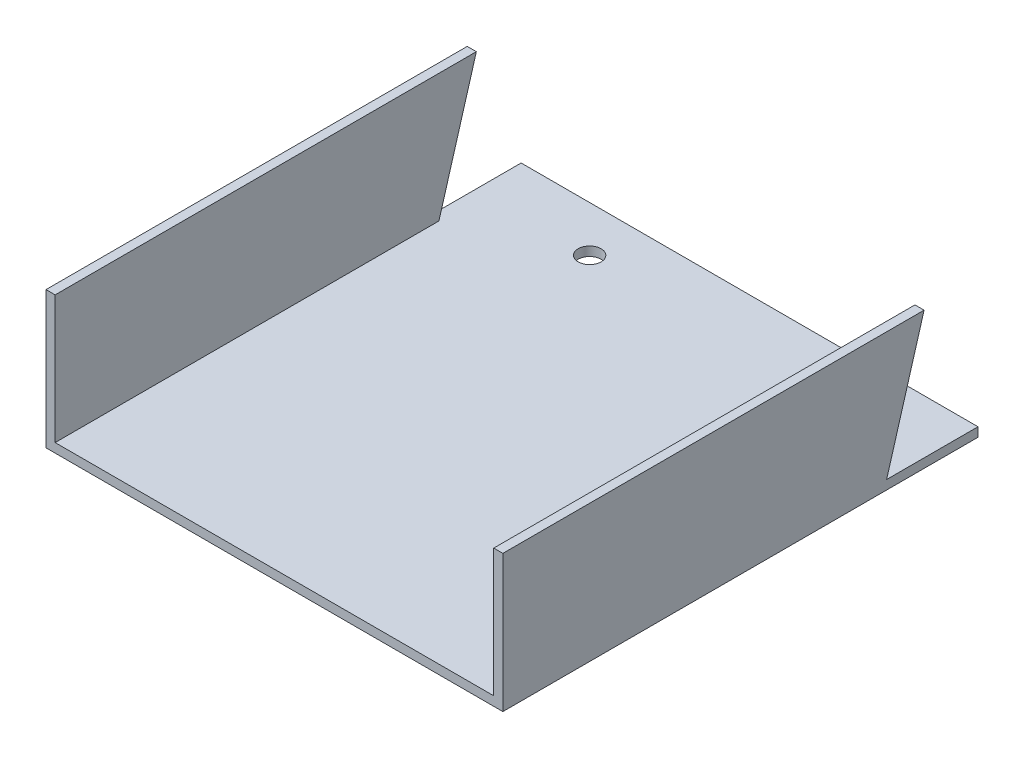
SolidWorks part; units mm, degrees
ref_plane "Front Plane" through (0, 0, 0) normal (0, 0, 1) x (1, 0, 0)
ref_plane "Top Plane" through (0, 0, 0) normal (0, 1, 0) x (1, 0, 0)
ref_plane "Right Plane" through (0, 0, 0) normal (1, 0, 0) x (0, 0, -1)
sketch "Sketch1" plane through (0, 0, 0) normal (0, 0, 1) x (1, 0, 0)
  line L0 (0, 0) -> (127, 0)
  line L1 (127, 0) -> (127, 38.1)
  line L2 (127, 38.1) -> (0, 38.1)
  line L3 (0, 38.1) -> (0, 0)
  dimension "D1" = 127
  dimension "D2" = 38.1
extrude "Boss-Extrude1" add sketch "Sketch1" along normal blind 132.08
sketch "Sketch2" plane through (0, 38.1, 0) normal (0, 1, 0) x (1, 0, 0)
  line L4 (0, -25.4) -> (2.54, -25.4)
  line L5 (2.54, -25.4) -> (2.54, -132.08)
  line L6 (63.5, 0) -> (63.5, -132.08) construction
  line L7 (124.46, -25.4) -> (124.46, -132.08)
  line L8 (127, 0) -> (0, 0)
  line L9 (0, 0) -> (0, -132.08)
  line L10 (0, -132.08) -> (127, -132.08)
  line L11 (127, -132.08) -> (127, 0)
  line L12 (127, 0) -> (0, 0)
  line L13 (0, 0) -> (0, -25.4)
  line L14 (2.54, -132.08) -> (124.46, -132.08)
  line L15 (127, -25.4) -> (127, 0)
  line L16 (127, -25.4) -> (124.46, -25.4)
  line L17 (0, -132.08) -> (0, 0) construction
  dimension "D2" = 25.4
  dimension "D3" = 2.54
  dimension "D1" = 0
extrude "Cut-Extrude1" cut sketch "Sketch2" against normal blind 35.56
sketch "Sketch3" plane through (0, 0, 0) normal (1, 0, 0) x (0, 0, -1)
  line L0 (-25.4, 2.54) -> (-14.986, 38.1)
  line L1 (-14.986, 38.1) -> (-25.4, 38.1)
  line L2 (-25.4, 38.1) -> (-25.4, 2.54)
  dimension "D1" = 10.414
extrude "Boss-Extrude2" add sketch "Sketch3" along normal blind 2.54
extrude "Boss-Extrude3" add sketch "Sketch3<2>" against normal blind 2.54 from surface starting at face at (127, 13.5467, 52.4933)
sketch "Sketch3<2>" plane through (0, 0, 0) normal (1, 0, 0) x (0, 0, -1) same geometry as "Sketch3"
sketch "Sketch4" plane through (0, 2.54, 0) normal (0, 1, 0) x (1, 0, 0)
  line L0 (0, -12.7) -> (127, -12.7) construction
  line L1 (0, 0) -> (0, -25.4) construction
  line L2 (127, -25.4) -> (127, 0) construction
  line L3 (127, 0) -> (0, 0) construction
  line L4 (63.5, 0) -> (63.5, -12.7) construction
  circle A0 centre (31.75, -12.7) radius 3.175
  circle A1 centre (95.25, -12.7) radius 3.175
  dimension "D2" = 6.35
  dimension "D1" = 12.7
  dimension "D3" = 31.75
extrude "Cut-Extrude2" cut sketch "Sketch4" against normal blind 2.54
